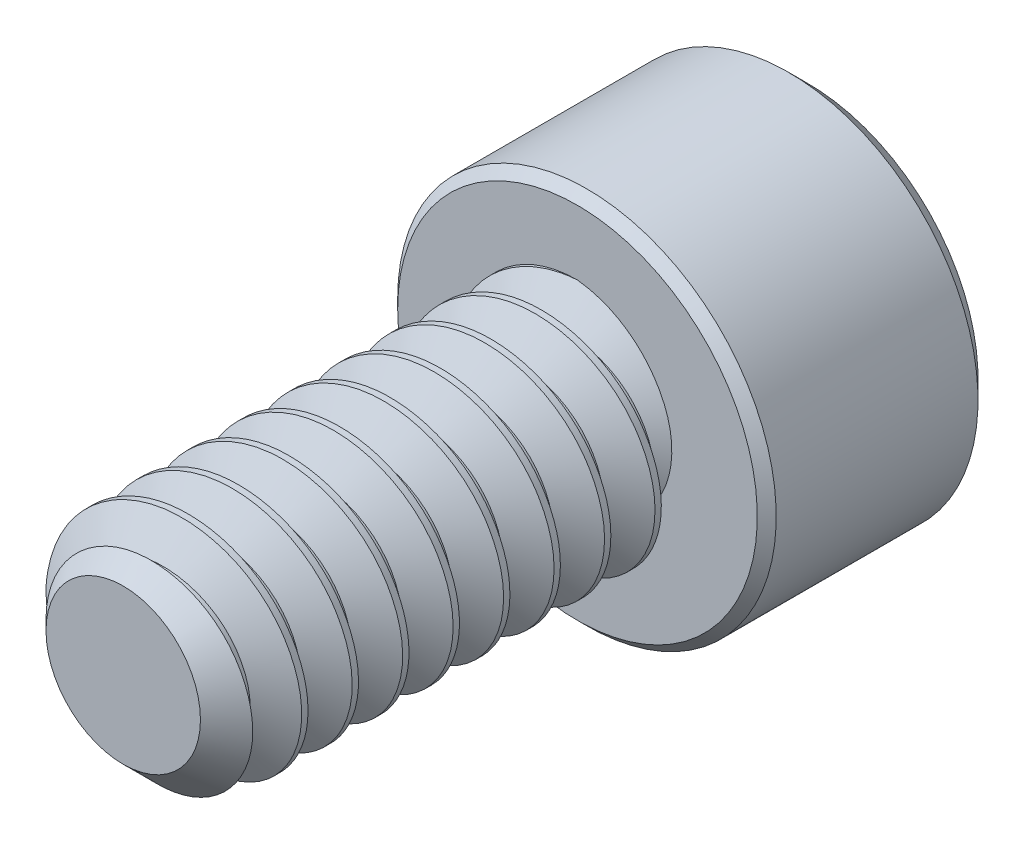
SolidWorks part; units mm, degrees
ref_plane "Front Plane" through (0, 0, 0) normal (0, 0, 1) x (1, 0, 0)
ref_plane "Top Plane" through (0, 0, 0) normal (0, 1, 0) x (1, 0, 0)
ref_plane "Right Plane" through (0, 0, 0) normal (1, 0, 0) x (0, 0, -1)
sketch "Sketch0" plane through (0, 0, 0) normal (1, 0, 0) x (0, 0, -1)
  line L0 (0, 0) -> (9.525, 0) construction
  point P2 (14.351, 0)
  point P4 (0, 0)
  dimension "D1" = 9.525
  dimension "D2" = 4.826
  dimension "Min Thread" = 0
sketch "Sketch1" plane through (0, 0, 0) normal (0, 0, 1) x (1, 0, 0)
  circle A0 centre (0, 0) radius 2.413
  dimension "OD" = 4.826
extrude "Extrude1" add sketch "Sketch1" against normal blind 9.525
sketch "Sketch2" plane through (0, 0, 0) normal (0, 0, 1) x (1, 0, 0)
  circle A0 centre (0, 0) radius 2.413 construction
  circle A1 centre (0, 0) radius 2.413
curve "Helix/Spiral1" pitch 1.0583 height 10.5833 turns 10 parameters "pitch"=1.0583
chamfer "Chamfer3" distance 0.7937 angle 45 1 edges at (2.413, 0, 0)
sketch "Sketch3" plane through (0, 0, 0) normal (1, 0, 0) x (0, 0, -1)
  line L0 (-0.926, 2.413) -> (-0.5292, 1.7256)
  line L1 (-0.5292, 1.7256) -> (-0.3969, 1.7256)
  line L2 (-0.3969, 1.7256) -> (0, 2.413)
  line L3 (-0.926, 2.413) -> (0, 2.413)
  line L4 (-0.463, 2.413) -> (-0.463, 1.7256) construction
  line L5 (-0.7276, 2.0693) -> (-0.1984, 2.0693) construction
  line L6 (0, 2.413) -> (0, -2.413) construction
  dimension "D1" = 0.1323
  dimension "D2" = 0.5292
  dimension "D3" = 60
sweep "Cut-Sweep1" cut profiles "Sketch3" path "Helix/Spiral1"
sketch "Sketch5" plane through (0, 0, 0) normal (1, 0, 0) x (0, 0, -1)
  line L0 (9.525, -1.7471) -> (9.525, 1.7217) construction
  line L1 (9.525, 2.413) -> (0, 2.413)
  line L2 (9.525, 2.413) -> (9.525, 0)
  line L3 (9.525, 0) -> (-0.8783, 0)
  line L4 (0, 0) -> (9.525, 0) construction
  line L5 (0, 2.413) -> (-0.8783, 0)
  line L6 (0, 0) -> (12.065, 0) construction
  dimension "D1" = 70
  dimension "D3" = 2.54
revolve "partially thread" [suppressed] add sketch "Sketch5" angle 360 about L6
sketch "Sketch6" plane through (0, 0, -9.525) normal (0, 0, -1) x (-1, 0, 0)
  circle A0 centre (0, 0) radius 3.9688
  dimension "head dia" = 7.9375
extrude "Extrude2" add sketch "Sketch6" along normal blind 4.826
sketch "Sketch7" plane through (0, 0, -14.351) normal (0, 0, -1) x (-1, 0, 0)
  line L1 (0, 2.2914) -> (-1.9844, 1.1457)
  line L2 (-1.9844, 1.1457) -> (-1.9844, -1.1457)
  line L3 (-1.9844, -1.1457) -> (0, -2.2914)
  line L4 (0, -2.2914) -> (1.9844, -1.1457)
  line L5 (1.9844, -1.1457) -> (1.9844, 1.1457)
  line L6 (1.9844, 1.1457) -> (0, 2.2914)
  circle A0 centre (0, 0) radius 1.9844 construction
  dimension "hex dia" = 3.9688
extrude "Cut-Extrude1" cut sketch "Sketch7" against normal blind 2.9766
sketch "Sketch8" plane through (0, 0, -14.351) normal (0, 0, -1) x (-1, 0, 0)
  circle A0 centre (0, 0) radius 2.2914
extrude "Cut-Extrude2" cut sketch "Sketch8" against normal through all draft 45
chamfer "Chamfer1" distance 0.3969 angle 45 1 edges at (-3.9688, 0, -14.351)
chamfer "Chamfer2" distance 0.1984 angle 45 1 edges at (-3.9688, 0, -9.525)
sketch "Sketch9" plane through (0, 0, 0) normal (1, 0, 0) x (0, 0, -1)
  line L0 (0, 2.413) -> (0, -2.413) construction
  line L1 (2.6458, 2.413) -> (2.6458, -2.413) construction
  line L2 (14.351, 3.9688) -> (14.351, -3.9688) construction
  line L3 (9.525, 3.9688) -> (9.525, -3.9688) construction
  line L4 (9.525, 3.7703) -> (9.525, -3.7703) construction
  line L5 (14.351, -3.5719) -> (14.351, 3.5719) construction
  line L6 (9.525, -3.9688) -> (9.525, 3.9688) construction
  line L7 (0, 1.6193) -> (0, -1.6193) construction
  line L8 (-0.926, 2.413) -> (0, 2.413) construction
  line L9 (2.6458, 0) -> (0, 0) construction
  dimension "D1" = 2.6458
equation "\"D3@Helix/Spiral1\" = \"screw length@Extrude1\"+\"pitch@Helix/Spiral1\""
equation "\"D1@Sketch3\" = \"pitch@Helix/Spiral1\"*.125"
equation "\"D2@Sketch3\" = \"pitch@Helix/Spiral1\"*.5"
equation "\"D1@Cut-Extrude1\" = \"hex dia@Sketch7\"*.75"
equation "\"D1@Chamfer1\" = \"head dia@Sketch6\"*.05"
equation "\"D1@Sketch9\" = \"pitch@Helix/Spiral1\"*2.50"
equation "\"D1@Chamfer2\" = \"D1@Chamfer1\"/2"
equation "\"D1@Chamfer3\" = \"pitch@Helix/Spiral1\"*.750"
equation "\"D1@Sketch0\" = \"screw length@Extrude1\""
equation "\"D2@Sketch0\" = \"head depth@Extrude2\""
